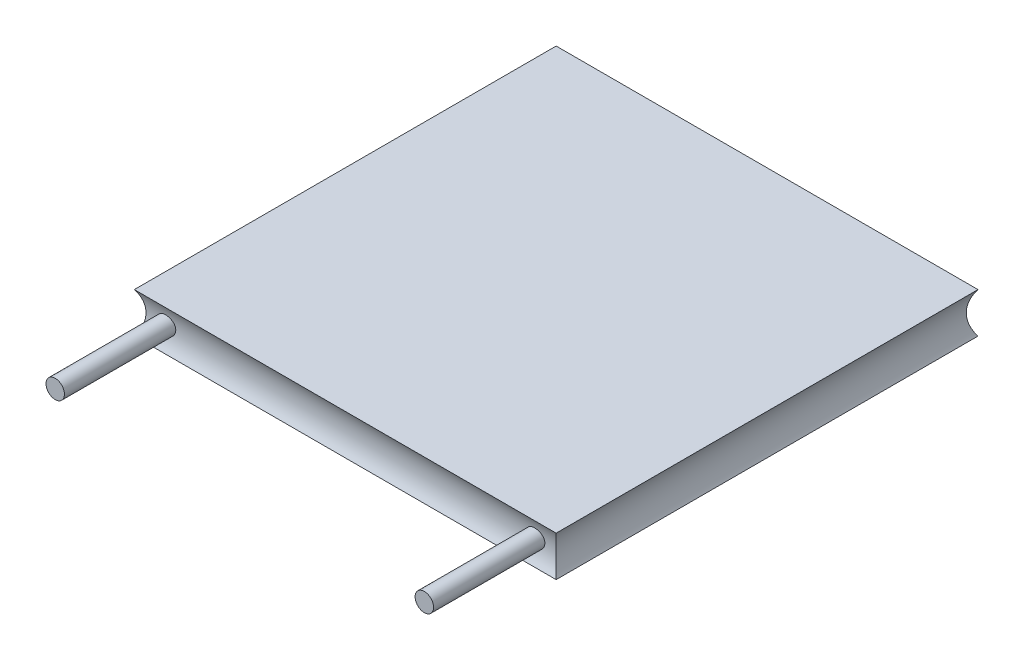
SolidWorks part; units mm, degrees
material "Ceramic Porcelain"
ref_plane "Front Plane" through (0, 0, 0) normal (0, 0, 1) x (1, 0, 0)
ref_plane "Top Plane" through (0, 0, 0) normal (0, 1, 0) x (1, 0, 0)
ref_plane "Right Plane" through (0, 0, 0) normal (1, 0, 0) x (0, 0, -1)
sketch "Sketch1" plane through (0, 0, 0) normal (0, 1, 0) x (1, 0, 0)
  line L1 (0, 0) -> (40, 0)
  line L2 (0, 0) -> (0, 40)
  line L3 (0, 40) -> (40, 40)
  line L4 (40, 0) -> (40, 40)
extrude "Boss-Extrude1" add sketch "Sketch1" along normal blind 3.82
sketch "Sketch2" plane through (0, 0, 0) normal (0, 0, 1) x (1, 0, 0)
  line L0 (0, 1.91) -> (-3, 1.91)
  line L1 (0, 3.82) -> (0, 0) construction
  line L2 (0, 0) -> (40, 0) construction
  line L3 (0, 3.82) -> (-3, 1.91)
  line L4 (0, 0) -> (-3, 1.91)
  line L5 (40, 1.91) -> (43, 1.91)
  line L6 (40, 3.82) -> (40, 0) construction
  line L7 (40, 3.82) -> (43, 1.91)
  line L8 (40, 0) -> (43, 1.91)
  arc A0 (0, 3.82) -> (0, 0) centre (-3, 1.91) cw
  arc A1 (40, 3.82) -> (40, 0) centre (43, 1.91) ccw
  line M6 (40, 0) -> (40, 3.82)
  line M8 (0, 3.82) -> (0, 0)
extrude "Cut-Extrude2" cut sketch "Sketch2" against normal through all contours L3 L0 M8 | A0 M8 | L4 L0 M8 | L7 L5 M6 | L8 L5 M6 | A1 M6 region at (-1, 1.2733, 0) region at (-1, 2.5467, 0) region at (0.2241, 1.91, 0) region at (41, 2.5467, 0) region at (41, 1.2733, 0) region at (39.7759, 1.91, 0)
sketch "Sketch3" plane through (0, 0, 0) normal (1, 0, 0) x (0, 0, -1)
  line L0 (40, 1.91) -> (43, 1.91)
  line L1 (40, 0) -> (40, 3.82) construction
  line L2 (0, 1.91) -> (-3, 1.91)
  line L3 (0, 3.82) -> (0, 0) construction
  line L4 (40, 3.82) -> (43, 1.91)
  line L5 (40, 0) -> (43, 1.91)
  line L6 (0, 3.82) -> (-3, 1.91)
  line L7 (0, 0) -> (-3, 1.91)
  arc A0 (0, 3.82) -> (0, 0) centre (-3, 1.91) cw
  arc A1 (40, 3.82) -> (40, 0) centre (43, 1.91) ccw
extrude "Cut-Extrude5" cut sketch "Sketch3" along normal blind 45 contours L4 A1 L5 | A0 L6 L7 region at (0, 2.821, -41.472) region at (0, 1.91, -0.5042)
sketch "Sketch4" plane through (0, 0, 0) normal (0, 0, 1) x (1, 0, 0)
  circle A0 centre (2.5, 1.91) radius 0.875
extrude "Boss-Extrude2" add sketch "Sketch4" along normal blind 10 and the other way blind 5
sketch "Sketch5" plane through (0, 0, 0) normal (0, 0, 1) x (1, 0, 0)
  circle A0 centre (37.5, 1.91) radius 0.875
extrude "Boss-Extrude3" add sketch "Sketch5" along normal blind 10 and the other way blind 5
ref_plane "Plane1" through (0, 0, -20) normal (0, 0, 1) x (1, 0, 0)
ref_plane "Plane2" through (20, 0, 0) normal (1, 0, 0) x (0, 0, -1)
